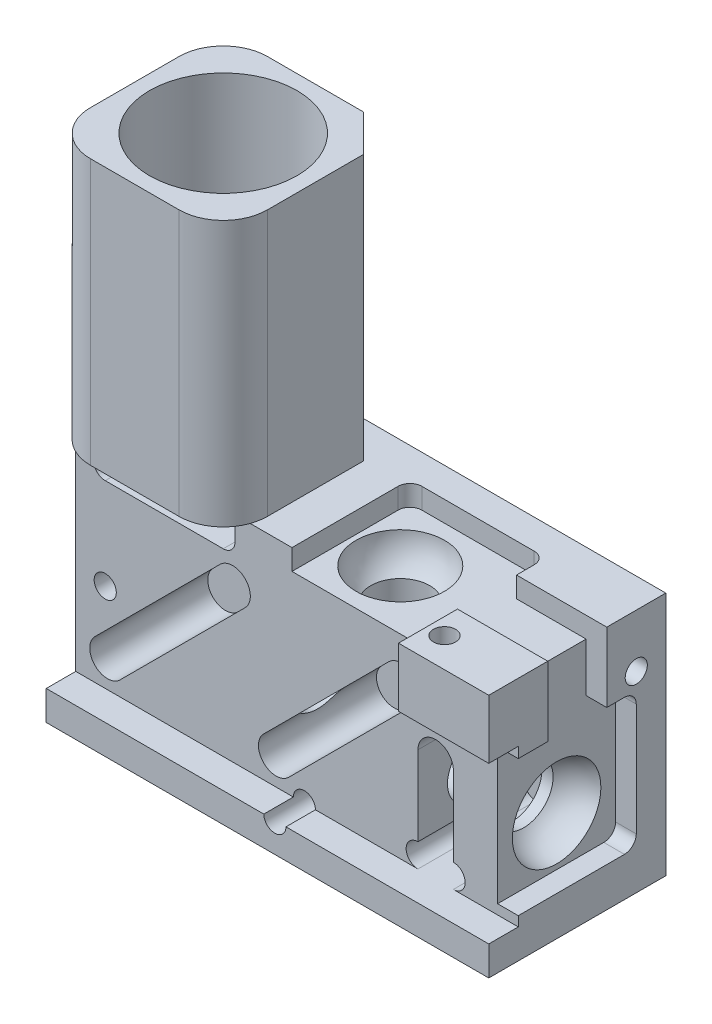
SolidWorks part; units mm, degrees
ref_plane "Front Plane" through (0, 0, 0) normal (0, 0, 1) x (1, 0, 0)
ref_plane "Top Plane" through (0, 0, 0) normal (0, 1, 0) x (1, 0, 0)
ref_plane "Right Plane" through (0, 0, 0) normal (1, 0, 0) x (0, 0, -1)
sketch "Sketch1" plane through (0, 0, 0) normal (0, 1, 0) x (1, 0, 0)
  line L1 (7.5, 3) -> (-7.5, 3)
  line L2 (7.5, 3) -> (7.5, -3)
  line L3 (7.5, -3) -> (-7.5, -3)
  line L4 (-7.5, 3) -> (-7.5, -3)
  line L5 (7.5, 3) -> (-7.5, -3) construction
  line L6 (7.5, -3) -> (-7.5, 3) construction
  point P0 (0, 0)
  dimension "D1" = 6
  dimension "D2" = 15
extrude "Main Body Ext" add sketch "Sketch1" along normal blind 8.3
sketch "Sketch8" plane through (0, 8.3, 0) normal (0, 1, 0) x (1, 0, 0)
  line L0 (-2.75, 3) -> (-1.5, 1.75)
  line L1 (-2.75, 3) -> (-7.5, 3)
  line L2 (-1.5, 1.75) -> (-1.5, -3)
  line L3 (-1.5, -3) -> (-7.5, -3)
  line L4 (-7.5, 3) -> (-7.5, -3)
  line L5 (-2.125, 2.375) -> (-7.5, -3) construction
  line L6 (-1.5, -3) -> (-7.5, 3) construction
  line L7 (-7.5, 3) -> (-7.5, -3) construction
  line L8 (0, 0) -> (-4.5, 0) construction
  point P0 (-4.5, 0)
  dimension "D1" = 6
  dimension "D2" = 6
  dimension "D3" = 1.25
  dimension "D4" = 3
extrude "Emission Path Ext" add sketch "Sketch8" along normal blind 9
sketch "Sketch3" plane through (0, 0, 0) normal (0, -1, 0) x (1, 0, 0)
  line L0 (-7.5, -3) -> (-7.5, 3) construction
  line L1 (0, 0) -> (-4.5, 0) construction
  circle A0 centre (-4.5, 0) radius 1.25
  dimension "D1" = 3
  dimension "D2" = 2.5
extrude "Emission and Grin Cut" cut sketch "Sketch3" against normal through all
sketch "Sketch4" plane through (7.5, 0, 0) normal (1, 0, 0) x (0, 0, -1)
  line L1 (-3, 0) -> (3, 0) construction
  circle A0 centre (0, 3) radius 1
  dimension "D1" = 2
  dimension "D2" = 3
extrude "Drum Lens Cut" cut sketch "Sketch4" against normal offset from surface (13 mm away) 2 up to face at (-7.5, 8.65, 0)
sketch "Sketch41" plane through (0, 8.3, 0) normal (0, 1, 0) x (1, 0, 0)
  line L1 (7.5, 3) -> (-2.75, 3) construction
  line L2 (-1.5, -3) -> (-1.5, 1.75) construction
  circle A0 centre (1.5, 0) radius 1
  dimension "D1" = 2
  dimension "D2" = 3
  dimension "D3" = 3
extrude "Addtl Light Source" cut sketch "Sketch41" against normal blind 5
sketch "Sketch5" plane through (0, 0, 3) normal (0, 0, 1) x (1, 0, 0)
  line L0 (-7.5, 0) -> (7.5, 0) construction
  line L1 (7.5, 8.3) -> (-7.5, 8.3)
  line L2 (7.5, 8.3) -> (7.5, 1)
  line L3 (7.5, 1) -> (-7.5, 1)
  line L4 (-7.5, 8.3) -> (-7.5, 1)
  line L5 (7.5, 8.3) -> (-7.5, 1) construction
  line L6 (7.5, 1) -> (-7.5, 8.3) construction
  line L7 (-1.5, 8.3) -> (7.5, 8.3) construction
  line L9 (7.5, 8.3) -> (7.5, 0) construction
  line L10 (-7.5, 17.3) -> (-7.5, 0) construction
  point P0 (0, 4.65)
  dimension "D1" = 1
extrude "FilterCover Cut1" cut sketch "Sketch5" against normal blind 1
sketch "Top-LED-Screw" plane through (0, 0, 2) normal (0, 0, 1) x (1, 0, 0)
  line L1 (7.5, 8.3) -> (4.44, 8.3)
  line L2 (7.5, 8.3) -> (7.5, 6.3)
  line L3 (7.5, 6.3) -> (4.44, 6.3)
  line L4 (4.44, 8.3) -> (4.44, 6.3)
  dimension "D1" = 2
  dimension "D2" = 3.06
extrude "Boss-Extrude1" add sketch "Top-LED-Screw" along normal blind 1
sketch "Sketch6" plane through (0, 0, 2) normal (0, 0, 1) x (1, 0, 0)
  line L0 (5.3, 4.5) -> (5.3, 1.8)
  line L1 (4.1, 4.5) -> (5.3, 4.5) construction
  line L2 (5.3, 1) -> (4.1, 1)
  line L3 (-7.5, 1) -> (7.5, 1) construction
  line L4 (-7.5, 8.3) -> (-7.5, 1) construction
  line L5 (-6.9, 7.9) -> (-6.9, 7.5)
  line L6 (4.1, 4.5) -> (4.1, 1.8)
  line L7 (-1.5, 8.3) -> (-7.5, 8.3) construction
  line L8 (-2.1, 7.9) -> (-2.1, 7.5)
  line L9 (-6, 1.5) -> (-6, 1) construction
  line L10 (-2.5, 8.3) -> (-6.5, 8.3)
  line L11 (-4.5, 3) -> (-4.5, 1) construction
  line L12 (-4.5, 3) -> (0.4851, 3) construction
  line L13 (-2.5, 7.1) -> (-6.5, 7.1)
  line L14 (-0.282, 1.5) -> (-0.282, 1) construction
  line L15 (-2.5, 8.3) -> (-6.5, 7.1) construction
  line L16 (-2.5, 7.1) -> (-6.5, 8.3) construction
  line L17 (4.1, 1.8) -> (5.3, 1.8) construction
  line L18 (-2.6059, 6.5912) -> (-6.8485, 2.3485)
  line L19 (7.5, 1) -> (7.5, 6.3) construction
  line L20 (-1.7574, 5.7426) -> (-6, 1.5)
  line L21 (-2.6059, 6.5912) -> (-6, 1.5) construction
  line L22 (-6.8485, 2.3485) -> (-1.7574, 5.7426) construction
  line L23 (1.826, 3.6081) -> (1.826, 1.6081) construction
  line L24 (1.826, 3.6081) -> (3.2165, 3.6081) construction
  line L25 (3.1121, 6.5912) -> (-1.1305, 2.3485)
  line L26 (3.9606, 5.7426) -> (-0.282, 1.5)
  line L27 (3.1121, 6.5912) -> (-0.282, 1.5) construction
  line L28 (-1.1305, 2.3485) -> (3.9606, 5.7426) construction
  line L33 (-2.5, 8.3) -> (1.102, 8.3) construction
  line L34 (1.102, 8.3) -> (1.102, 7.1) construction
  line L35 (1.102, 7.1) -> (-2.5, 7.1) construction
  line L36 (-6.5, 7.1) -> (-4.098, 7.1) construction
  line L37 (-4.098, 7.1) -> (-4.098, 8.3) construction
  line L38 (-4.098, 8.3) -> (-6.5, 8.3) construction
  line L39 (-6.5, 8.3) -> (-2.7284, 6.992) construction
  arc A0 (-2.5, 8.3) -> (-2.1, 7.9) centre (-2.5, 7.9) cw
  arc A1 (4.1, 4.5) -> (5.3, 4.5) centre (4.7, 4.5) cw
  arc A2 (-6.5, 8.3) -> (-6.9, 7.9) centre (-6.5, 7.9) ccw
  arc A3 (-2.6059, 6.5912) -> (-1.7574, 5.7426) centre (-2.1816, 6.1669) cw
  arc A4 (4.1, 1) -> (4.1, 1.8) centre (4.1, 1.4) cw
  arc A5 (-6.8485, 2.3485) -> (-6, 1.5) centre (-6.4243, 1.9243) ccw
  arc A6 (5.3, 1) -> (5.3, 1.8) centre (5.3, 1.4) ccw
  arc A7 (-6.5, 7.1) -> (-6.9, 7.5) centre (-6.5, 7.5) cw
  arc A8 (-2.5, 7.1) -> (-2.1, 7.5) centre (-2.5, 7.5) ccw
  arc A9 (3.1121, 6.5912) -> (3.9606, 5.7426) centre (3.5364, 6.1669) cw
  arc A10 (-1.1305, 2.3485) -> (-0.282, 1.5) centre (-0.7063, 1.9243) ccw
  point P5 (-4.5, 7.7)
  point P10 (-4.3029, 4.0456)
  point P21 (1.415, 4.0456)
  dimension "D10" = 0.5
  dimension "D5" = 2.2
  dimension "D8" = 0.4
  dimension "D11" = 0.4
  dimension "D12" = 0.4
  dimension "D1" = 1.2
  dimension "D2" = 45
  dimension "D3" = 3.5
  dimension "D4" = 1.2
  dimension "D6" = 2
  dimension "D7" = 4
  dimension "D9" = 3
  dimension "D13" = 1.2
  dimension "D14" = 3
  dimension "D15" = 6
  dimension "D16" = 45
  dimension "D17" = 0.5
  dimension "D18" = 1.2
  dimension "D19" = 2
  dimension "D20" = 6
extrude "FilterSet Cut2" cut sketch "Sketch6" against normal offset from surface (4 mm away) 1 up to face at (-0.0625, 9.2833, -3)
sketch "Sketch10" plane through (0, 17.3, 0) normal (0, 1, 0) x (1, 0, 0)
  line L0 (-4.5, 0) -> (-4.5, -3) construction
  line L1 (-7.5, -3) -> (-1.5, -3) construction
  line L3 (-4.5, 0) -> (-7.5, 0) construction
  line L4 (-7.5, 3) -> (-7.5, -3) construction
  circle A0 centre (-4.5, 0) radius 2.5
  dimension "D1" = 5
extrude "Emission Lens Cut" cut sketch "Sketch10" against normal offset from surface (8.5 mm away) 0.5 up to face at (-4.125, 8.3, 1.3125)
sketch "Sketch12" plane through (7.5, 0, 0) normal (1, 0, 0) x (0, 0, -1)
  line L0 (0, 3.635) -> (0, 0) construction
  line L1 (1.6, 5.94) -> (-1.6, 5.94)
  line L2 (1.6, 5.94) -> (1.6, 1.33) construction
  line L3 (-2, 1.33) -> (1.6, 1.33)
  line L4 (-1.6, 5.94) -> (-1.6, 1.33) construction
  line L5 (1.6, 5.94) -> (-1.6, 1.33) construction
  line L6 (1.6, 1.33) -> (-1.6, 5.94) construction
  line L7 (-3, 0) -> (3, 0) construction
  line L9 (-1.6, 5.94) -> (-2, 5.94)
  line L10 (-2, 1) -> (-2, 6.3) construction
  line L11 (-2, 5.94) -> (-2, 1.33)
  line L12 (2, 5.54) -> (2, 1.73)
  arc A1 (1.6, 5.94) -> (2, 5.54) centre (1.6, 5.54) cw
  arc A2 (1.6, 1.33) -> (2, 1.73) centre (1.6, 1.73) ccw
  circle A3 centre (0, 3) radius 1 construction
  point P0 (0, 3.635)
  dimension "D2" = 4.61
  dimension "D3" = 1.67
  dimension "D1" = 3.2
  dimension "D4" = 0.4
sketch "Sketch15" plane through (0, 0, 0) normal (0, -1, 0) x (1, 0, 0)
  line L0 (-6.25, 1.875) -> (-6.25, -1.875) construction
  line L2 (-1.5, 0) -> (-4.5, 0) construction
  line L3 (-4.5, 0) -> (-6.25, 0) construction
  circle A0 centre (-6.25, -1.875) radius 0.795
  circle A1 centre (-6.25, 1.875) radius 0.795
  circle A2 centre (-1.5, 0) radius 0.795
  dimension "D4" = 1.59
  dimension "D1" = 3.75
  dimension "D2" = 3
  dimension "D3" = 1.75
extrude "Magnets Cut" cut sketch "Sketch15" against normal blind 0.9
sketch "Sketch18" plane through (0, 0, 2) normal (0, 0, 1) x (1, 0, 0)
  line L0 (-7.5, 8.3) -> (-7.5, 1) construction
  line L1 (7.5, 1) -> (7.5, 6.3) construction
  line L2 (4.44, 8.3) -> (-1.5, 8.3) construction
  line L3 (-7.5, 0) -> (7.5, 0) construction
  line L7 (-7.5, 1) -> (4.1, 1) construction
  line L9 (-7.5, 1) -> (-7.5, 0) construction
  circle A0 centre (-6.5, 4) radius 0.375
  circle A1 centre (6, 5.8) radius 0.375
  circle A2 centre (0.25, 1) radius 0.375
  dimension "D1" = 0.75
  dimension "D2" = 1
  dimension "D3" = 2.5
  dimension "D4" = 1.5
  dimension "D5" = 3
  dimension "D6" = 1
  dimension "D7" = 7.75
extrude "Screw Holes Cut" cut sketch "Sketch18" against normal blind 2.5 and the other way through all
fillet "External Fillet 1" radius 1.5 2 edges at (-7.5, 8.65, -3)
sketch "Sketch28" plane through (0, 7.1, 0) normal (0, 1, 0) x (1, 0, 0)
  circle A0 centre (-4.5, 0) radius 1.5
  dimension "D1" = 3
extrude "Vertical-Path-Cut" cut sketch "Sketch28" against normal blind 4 and the other way through all
extrude "Cut-Extrude Original Light" cut sketch "Sketch12" against normal blind 0.7
sketch "Sketch44" plane through (0, 8.3, 0) normal (0, 1, 0) x (1, 0, 0)
  line L0 (-0.17, -2) -> (4.44, -2)
  line L1 (-0.17, -2) -> (-0.17, 1.6)
  line L2 (4.44, -2) -> (4.44, 1.6)
  line L3 (0.23, 2) -> (4.04, 2)
  line L6 (4.44, -2) -> (-1.5858, -2) construction
  circle A0 centre (1.5, 0) radius 1 construction
  arc A1 (4.44, 1.6) -> (4.04, 2) centre (4.04, 1.6) ccw
  arc A2 (-0.17, 1.6) -> (0.23, 2) centre (0.23, 1.6) cw
  point P10 (4.44, 2)
  point P13 (-0.17, 2)
  dimension "D3" = 1.67
  dimension "D4" = 0.4
  dimension "D5" = 0.4
  dimension "D1" = 4
  dimension "D2" = 4.61
extrude "Cut-Extrude Addtl Light" cut sketch "Sketch44" against normal blind 0.7
sketch "Sketch29" plane through (7.5, 0, 0) normal (1, 0, 0) x (0, 0, -1)
  line L0 (3, 8.3) -> (3, 0) construction
  line L1 (-3, 8.3) -> (3, 8.3) construction
  circle A0 centre (2, 6.5) radius 0.375
  circle A1 centre (0, 3) radius 1 construction
  dimension "D1" = 0.75
  dimension "D2" = 1
  dimension "D3" = 1.8
  dimension "D5" = 3.5
  dimension "D6" = 2
extrude "Side-LED-Screw" cut sketch "Sketch29" against normal blind 2.5
sketch "Sketch31" plane through (6.8, 0, 0) normal (1, 0, 0) x (0, 0, -1)
  circle A0 centre (0, 3) radius 1.6
  dimension "D1" = 3.2
sketch "Sketch32" plane through (7.5, 0, 0) normal (1, 0, 0) x (0, 0, -1)
  line L0 (-3, 8.3) -> (3, 8.3) construction
  line L1 (-1, 8.3) -> (1, 8.3)
  line L2 (-1, 8.3) -> (-1, 5.94)
  line L3 (-1, 5.94) -> (1, 5.94)
  line L4 (1, 8.3) -> (1, 5.94)
  line L5 (1.6, 5.94) -> (-2, 5.94) construction
  line L6 (-2, 5.94) -> (-2, 6.3) construction
  line L8 (3, 8.3) -> (3, 0) construction
  dimension "D1" = 1
  dimension "D2" = 2
extrude "Side-Wire-Slot-Cut" cut sketch "Sketch32" against normal up to surface (0.7 mm away) up to face at (6.8, 3.635, -0.5609)
sketch "Sketch45" plane through (0, 8.3, 0) normal (0, 1, 0) x (1, 0, 0)
  line L1 (4.44, -1) -> (6.8, -1)
  line L2 (4.44, -1) -> (4.44, 1)
  line L3 (4.44, 1) -> (6.8, 1)
  line L4 (6.8, -1) -> (6.8, 1)
  line L5 (4.44, -1) -> (6.8, 1) construction
  line L6 (4.44, 1) -> (6.8, -1) construction
  line L7 (6.8, 1) -> (6.8, -1) construction
  line L8 (4.44, -3) -> (4.44, 1.6) construction
  line L12 (6.8, -1) -> (7.5, -1) construction
  line L13 (6.8, 1) -> (7.5, 1) construction
extrude "Top-LED-slot" cut sketch "Sketch45" against normal blind 0.7
sketch "Sketch33" plane through (0, 0, 0) normal (0, 0, 1) x (1, 0, 0)
  line L0 (6.8, 3) -> (5.3, 3)
  line L1 (6.8, 1.4) -> (6.8, 4.6) construction
  line L2 (6.8, 3) -> (6.8, 4.5)
  arc A0 (5.3, 3) -> (6.8, 4.5) centre (6.8, 3) cw
  dimension "D2" = 1.5
revolve "Side-BallLens_Cut" cut sketch "Sketch33" angle 360 about L0
sketch "Sketch46" plane through (0, 7.6, 0) normal (0, 1, 0) x (1, 0, 0)
  circle A0 centre (1.5, 0) radius 1.5 construction
ref_plane "Plane1" through (1.5, 0, 0) normal (1, 0, 0) x (0, 0, -1)
sketch "Sketch47" plane through (1.5, 0, 0) normal (1, 0, 0) x (0, 0, -1)
  line L4 (-1.5, 7.6) -> (0, 7.6)
  line L5 (0, 7.6) -> (0, 6.1373)
  line L6 (1, 7.6) -> (-1, 7.6) construction
  arc A0 (0, 6.1373) -> (-1.5, 7.6) centre (0, 7.6378) cw
revolve "Top-BallLens_Cut" cut sketch "Sketch47" angle 360 about L5
sketch "Sketch36" plane through (0, 17.3, 0) normal (0, 1, 0) x (1, 0, 0)
  line L0 (-7.5, -1.5) -> (-7.5, -3)
  line L1 (-7.5, 1.5) -> (-7.5, -3) construction
  line L2 (-7.5, -3) -> (-6, -3)
  line L3 (-7.5, -3) -> (-3, -3) construction
  arc A0 (-7.5, -1.5) -> (-6, -3) centre (-6, -1.5) ccw
  dimension "D1" = 1.5
  dimension "D2" = 1.5
extrude "Cut-Extrude16" cut sketch "Sketch36" against normal up to surface (9 mm away) up to face at (-4.3971, 8.3, 1.2781)
sketch "Sketch37" plane through (0, 8.8, 0) normal (0, 1, 0) x (1, 0, 0)
  circle A0 centre (-4.5, 0) radius 2
  circle A1 centre (-4.5, 0) radius 1.5 construction
  dimension "D1" = 4
extrude "Cut-Extrude17" cut sketch "Sketch37" against normal up to next
sketch "Sketch51" plane through (0, 8.3, 0) normal (0, 1, 0) x (1, 0, 0)
  circle A0 centre (5, -2) radius 0.375
  circle A1 centre (1.5, 0) radius 1.5 construction
  dimension "D1" = 0.75
  dimension "D2" = 3.5
  dimension "D3" = 2
extrude "Top-LE-Screw" cut sketch "Sketch51" against normal blind 2.1
sketch "Notch" plane through (0, 0, 0) normal (0, -1, 0) x (1, 0, 0)
  line L0 (4.1286, -3) -> (3, -2.2476) construction
  line L1 (7.5, -3) -> (-6, -3) construction
  line L2 (3, -2.2476) -> (2.5865, -2.2476) construction
  line L3 (2.5865, -2.2476) -> (2.0849, -3) construction
  line L4 (3, -2.2476) -> (4.0396, -2.9406) construction
  line L5 (3, -2.2476) -> (2, -2.2476) construction
  line L6 (1.8849, -2.0476) -> (1.8849, -3)
  line L7 (4.4892, -3) -> (3.0606, -2.0476)
  line L8 (3.0606, -2.0476) -> (1.8849, -2.0476)
  line L9 (1.8849, -2.0476) -> (1.05, -3.3)
  line L10 (4.4892, -3) -> (1.8849, -3)
  line L12 (4.0396, -2.9406) -> (2.6528, -5.0208) construction
  line L13 (2.0849, -3) -> (2.0849, -2.2476) construction
  line L14 (2.0849, -2.2476) -> (2.5865, -2.2476) construction
  point P14 (0, 0)
  point P19 (0, 0)
  point P20 (0, 0)
  point P21 (2.4449, 3.2932)
  line M13 (-6, -3) -> (7.5, -3)
  dimension "D1" = 0.2
  dimension "D2" = 0.2
  dimension "D3" = 0.2
extrude "Notch-Extrude" cut sketch "Notch" against normal blind 2 contours L7 L8 L6 M13 | L6 L9 M13 region at (2.8749, 0, -2.5838) region at (1.6733, 0, -2.6825)
